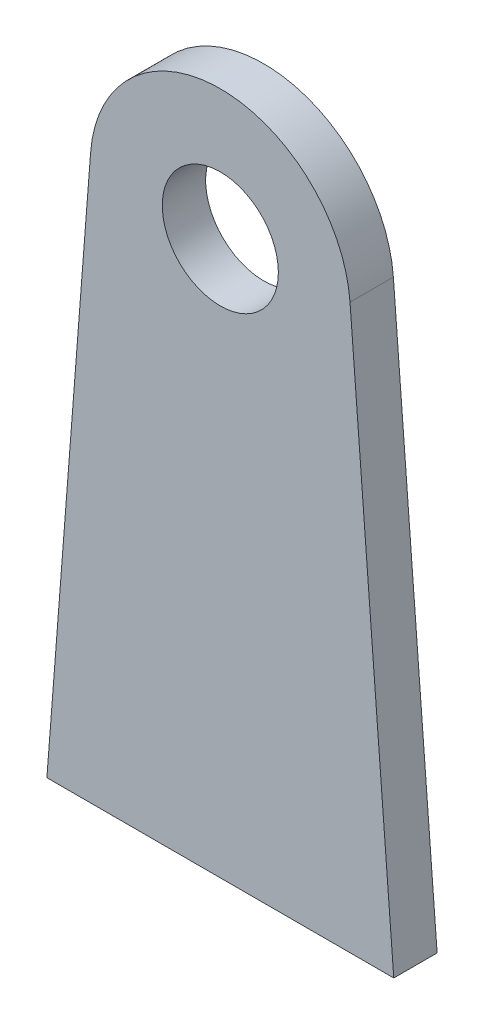
SolidWorks part; units mm, degrees
ref_plane "Front Plane" through (0, 0, 0) normal (0, 0, 1) x (1, 0, 0)
ref_plane "Top Plane" through (0, 0, 0) normal (0, 1, 0) x (1, 0, 0)
ref_plane "Right Plane" through (0, 0, 0) normal (1, 0, 0) x (0, 0, -1)
sketch "Sketch1" plane through (0, 0, 0) normal (0, 0, 1) x (1, 0, 0)
  line L0 (0, 0) -> (0, -35.9042) construction
  line L1 (-12.7, -35.9042) -> (12.7, -35.9042)
  line L2 (12.7, -35.9042) -> (9.4888, 0.8295)
  line L3 (-12.7, -35.9042) -> (-9.4888, 0.8295)
  line L6 (2.4398, -45.0067) -> (-67.8292, 217.1568) construction
  circle A0 centre (0, 0) radius 4.25
  circle A1 centre (0, 0) radius 9.525
  dimension "D2" = 8.5
  dimension "D3" = 19.05
  dimension "D1" = 12.7
extrude "Boss-Extrude1" [suppressed] add sketch "Sketch1" along normal blind 3.175 contours A0 A1 | L0 A1 L3 L1 | A1 L0 L1 L2
sketch "Sketch2" plane through (0, 0, 0) normal (0, 0, 1) x (1, 0, 0)
  line L0 (1.1534, 0.3092) -> (1.1534, -40.2074) construction
  line L1 (-11.5466, -40.2074) -> (13.8534, -40.2074)
  line L2 (13.8534, -40.2074) -> (10.6498, 1.0466)
  line L3 (-11.5466, -40.2074) -> (-8.343, 1.0466)
  circle A0 centre (1.1534, 0.3092) radius 4.25
  circle A1 centre (1.1534, 0.3092) radius 9.525
  dimension "D2" = 8.5
  dimension "D3" = 19.05
  dimension "D1" = 12.7
extrude "Boss-Extrude2" add sketch "Sketch2" along normal blind 3.175 contours A0 A1 | L0 A1 L3 L1 | A1 L0 L1 L2 region at (-5.6399, -5.9771, 0) region at (7.0464, -24.1268, 0) region at (-4.7396, -24.1268, 0)
